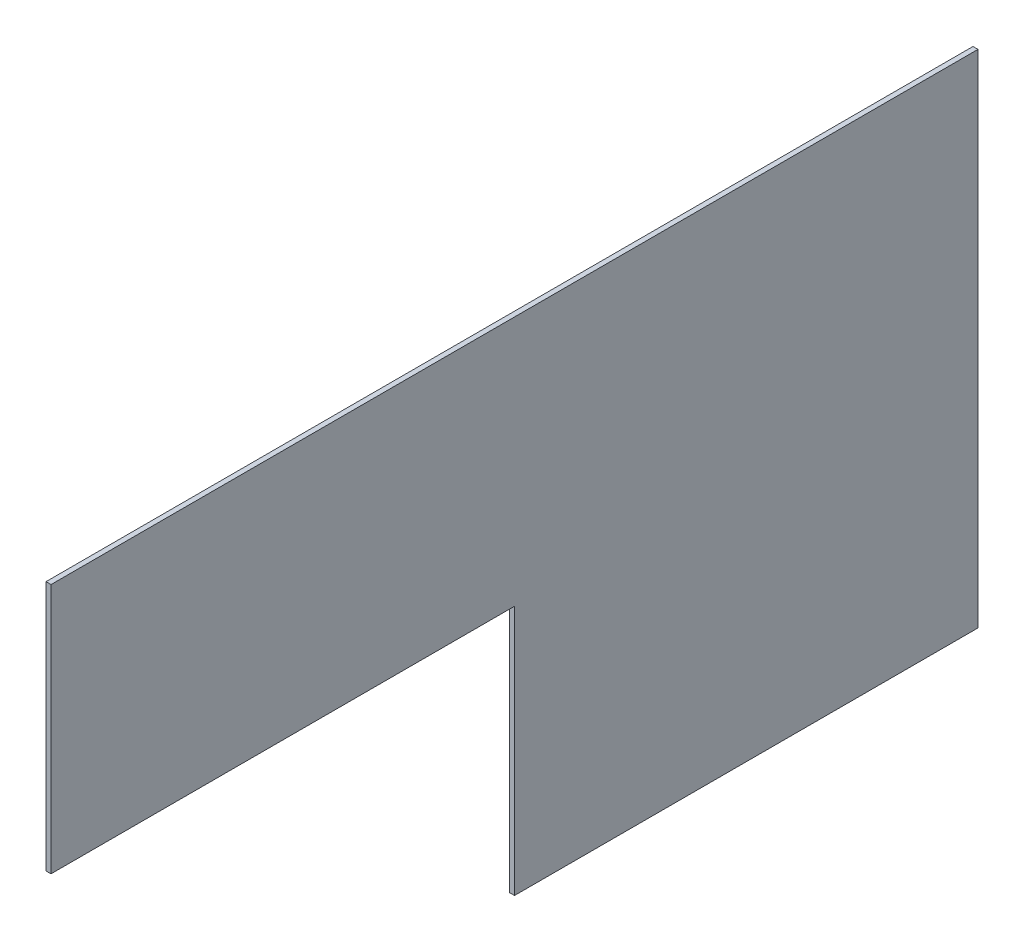
SolidWorks part; units mm, degrees
note: The reader was unsure of these and kept them because the rebuilt part matched: thickness of "Base-Flange1", "Sheet-Metal3".
material "AISI 304"
ref_plane "Front Plane" through (0, 0, 0) normal (0, 0, 1) x (1, 0, 0)
ref_plane "Top Plane" through (0, 0, 0) normal (0, 1, 0) x (1, 0, 0)
ref_plane "Right Plane" through (0, 0, 0) normal (1, 0, 0) x (0, 0, -1)
sketch "Sketch1" plane through (0, 0, 0) normal (1, 0, 0) x (0, 0, -1)
  line L0 (0, 0) -> (0, -100)
  line L1 (0, -100) -> (185, -100)
  line L2 (185, -100) -> (185, -200)
  line L3 (185, -200) -> (370, -200)
  line L4 (370, -200) -> (370, 0)
  line L5 (0, 0) -> (370, 0)
  dimension "D1" = 370
  dimension "D2" = 200
  dimension "D3" = 185
  dimension "D4" = 100
base flange "Base-Flange1" sketch "Sketch1" thickness 2 reverse thickness direction no parameters "D1"=2.5
sketch "Bend-Lines1" [suppressed] plane through (0, 0, 0) normal (0, 1, 0) x (1, 0, 0)
sketch "Bounding-Box1" [suppressed] plane through (0, 0, 0) normal (0, 1, 0) x (1, 0, 0)
sheet metal parameters "Sheet-Metal3" thickness 2 parameters "D1"=2.5
flat pattern "Flat-Pattern3" [suppressed]
sketch "Bend-Lines2" plane through (0, 0, 0) normal (0, 1, 0) x (1, 0, 0)
sketch3d "Bounding-Box2" [suppressed]
  line L0 (0, -200, 0) -> (370, -200, 0) construction
  line L1 (0, 0, 0) -> (370, 0, 0) construction
  line L2 (0, -200, 0) -> (0, 0, 0) construction
  line L3 (370, -200, 0) -> (370, 0, 0) construction
